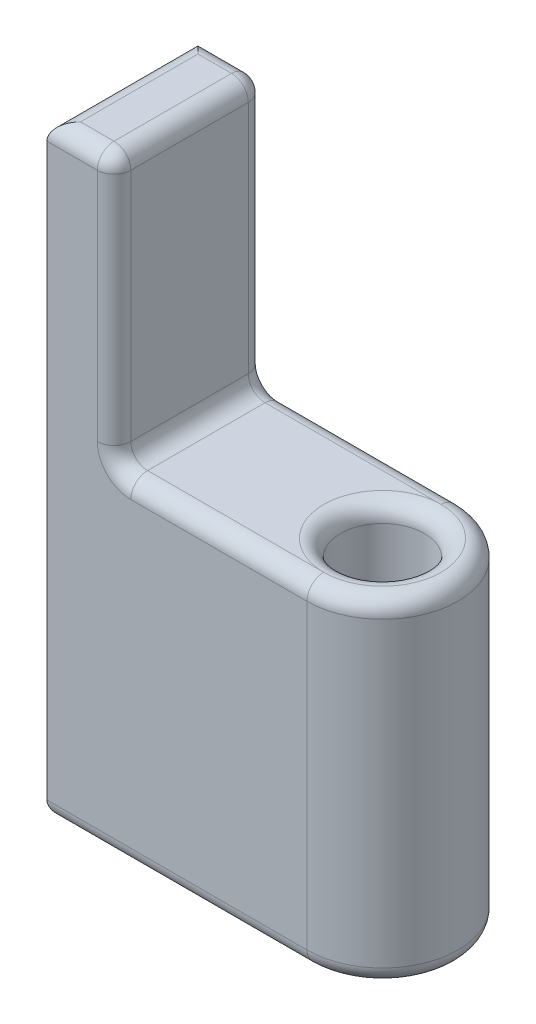
SolidWorks part; units mm, degrees
ref_plane "Front Plane" through (0, 0, 0) normal (0, 0, 1) x (1, 0, 0)
ref_plane "Top Plane" through (0, 0, 0) normal (0, 1, 0) x (1, 0, 0)
ref_plane "Right Plane" through (0, 0, 0) normal (1, 0, 0) x (0, 0, -1)
sketch "Sketch1" plane through (0, 0, 0) normal (0, 1, 0) x (1, 0, 0)
  line L1 (0, 0) -> (15.5, 0)
  line L2 (0, 0) -> (0, 9)
  line L3 (0, 9) -> (15.5, 9)
  arc A0 (15.5, 0) -> (15.5, 9) centre (15.5, 4.5) ccw
  circle A1 centre (15.5, 4.5) radius 2.5
  point P7 (10, 4.5)
  point P8 (10, 0)
  point P9 (0, 0)
  dimension "D1" = 4.5
  dimension "D2" = 5
  dimension "D3" = 15.5
extrude "Boss-Extrude1" add sketch "Sketch1" along normal blind 20
sketch "Sketch2" plane through (0, 20, 0) normal (0, 1, 0) x (1, 0, 0)
  line L0 (0, 0) -> (15.5, 0) construction
  line L1 (0, 9) -> (4, 9)
  line L2 (0, 9) -> (0, 0)
  line L3 (0, 0) -> (4, 0)
  line L4 (4, 9) -> (4, 0)
  dimension "D1" = 4
extrude "Boss-Extrude2" add sketch "Sketch2" along normal blind 16
fillet "Fillet1" radius 1 16 edges at (4, 28, -9) (4, 28, 0) (15.5, 0, -2) (7.75, 0, 0) (20, 0, -4.5) (7.75, 0, -9) (0, 0, -4.5) (2, 36, -9) (4, 36, -4.5) (2, 36, 0) (0, 36, -4.5) (15.5, 20, -2) (9.75, 20, -9) (20, 20, -4.5) (9.75, 20, 0) (4, 20, -4.5)
